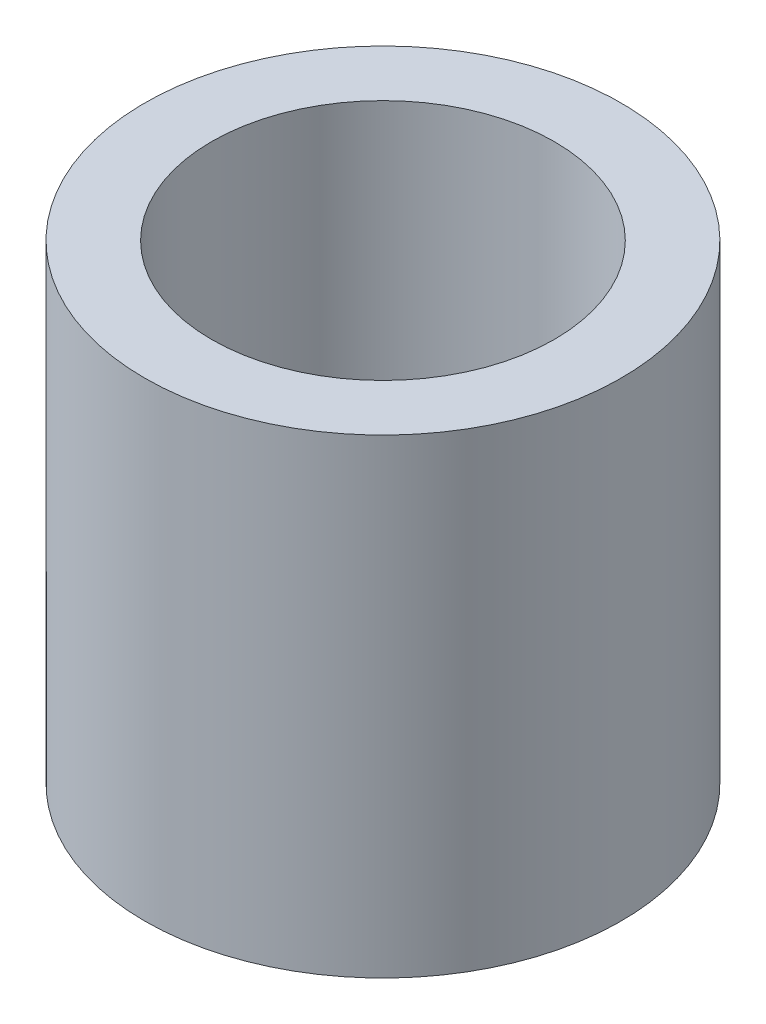
SolidWorks part; units mm, degrees
ref_plane "Front Plane" through (0, 0, 0) normal (0, 0, 1) x (1, 0, 0)
ref_plane "Top Plane" through (0, 0, 0) normal (0, 1, 0) x (1, 0, 0)
ref_plane "Right Plane" through (0, 0, 0) normal (1, 0, 0) x (0, 0, -1)
sketch "Sketch1" plane through (0, 0, 0) normal (0, 1, 0) x (1, 0, 0)
  circle A0 centre (0, 0) radius 22.5
  dimension "SLEEVE_OD" = 45
extrude "Boss-Extrude1" add sketch "Sketch1" along normal blind 44.4062
sketch "Sketch2" plane through (0, 0, 0) normal (0, 1, 0) x (1, 0, 0)
  circle A0 centre (0, 0) radius 16.1849
  dimension "BORE_D" = 32.3698
extrude "Cut-Extrude1" cut sketch "Sketch2" along normal through all
chamfer "Chamfer1" distance 3.232 angle 60 rebuild error yes
